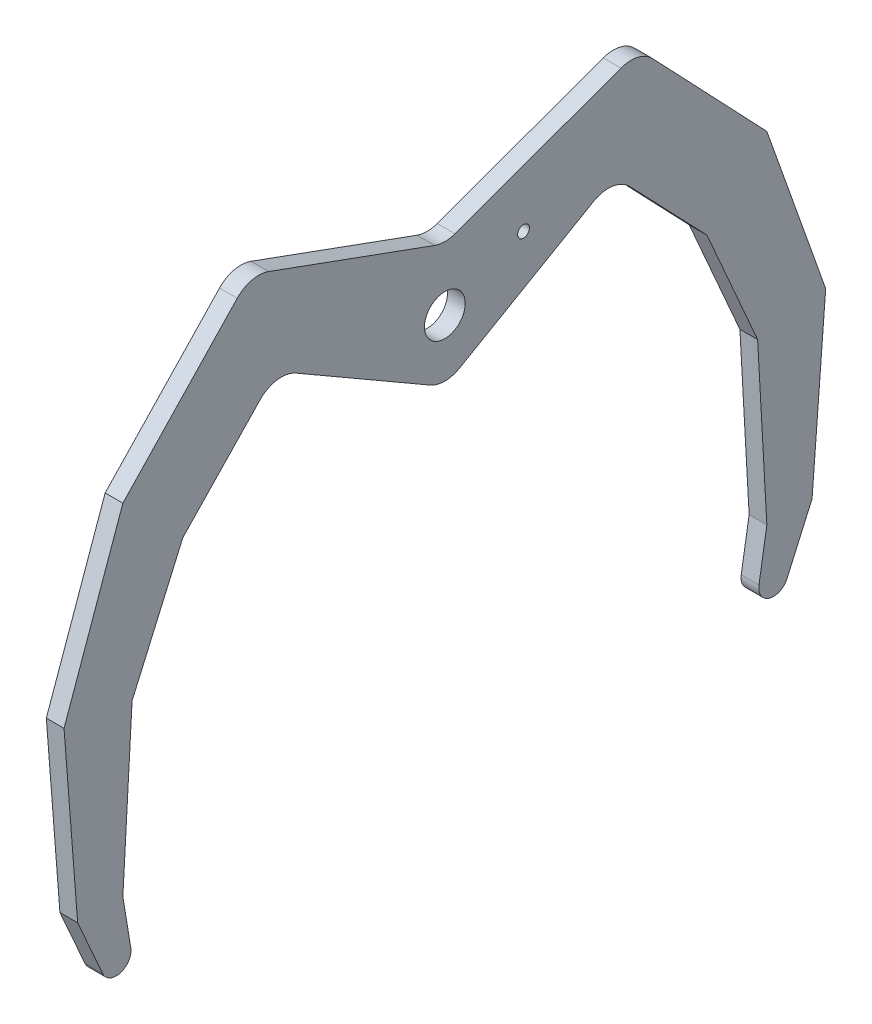
SolidWorks part; units mm, degrees
ref_plane "Front Plane" through (0, 0, 0) normal (0, 0, 1) x (1, 0, 0)
ref_plane "Top Plane" through (0, 0, 0) normal (0, 1, 0) x (1, 0, 0)
ref_plane "Right Plane" through (0, 0, 0) normal (1, 0, 0) x (0, 0, -1)
sketch "Sketch1" plane through (0, 0, 0) normal (1, 0, 0) x (0, 0, -1)
  line L0 (0, 15.8908) -> (0, -85.45) construction
  line L1 (1.7101, 11.0724) -> (29.8122, 21.3008)
  line L2 (2.5, -9.0066) -> (25.1791, 4.0871)
  line L3 (0, -85.45) -> (50, -85.45) construction
  line L4 (44.3608, -10.45) -> (31.2923, 3.213)
  line L5 (44.3608, -10.45) -> (52.94, -30.0455)
  line L6 (52.94, -30.0455) -> (54.5035, -58.0021)
  line L7 (54.5035, -58.0021) -> (53.1654, -66.1575)
  line L8 (-62.1586, -58.0021) -> (-64.4625, -28.3423)
  line L9 (-52.94, -30.0455) -> (-54.5035, -58.0021)
  line L10 (-64.4625, -28.3423) -> (-54.5035, -0.3096)
  line L11 (-44.3608, -10.45) -> (-52.94, -30.0455)
  line L12 (-44.3608, -10.45) -> (-31.2923, 3.213)
  line L13 (-54.5035, -0.3096) -> (-35.1457, 20.0478)
  line L14 (-2.5, -9.0066) -> (-25.1791, 4.0871)
  line L15 (-1.7101, 11.0724) -> (-29.8122, 21.3008)
  line L16 (62.1586, -58.0021) -> (57.9182, -67.5748)
  line L17 (62.1586, -58.0021) -> (64.4625, -28.3423)
  line L18 (64.4625, -28.3423) -> (54.5035, -0.3096)
  line L19 (54.5035, -0.3096) -> (35.1457, 20.0478)
  line L20 (-50.0689, 18.9616) -> (-69.3664, -3.6794) [skipped]
  line L21 (-69.3664, -3.6794) -> (-77.7866, -32.2121) [skipped]
  line L22 (-77.7866, -32.2121) -> (-73.8735, -61.7028) [skipped]
  line L23 (-73.8735, -61.7028) -> (-58.3038, -87.0523) [skipped]
  line L24 (-58.3038, -87.0523) -> (-33.7696, -103.8774) [skipped]
  line L25 (6.5074, 32.6053) -> (-8.3617, 32.2008) [skipped]
  line L26 (-23.2308, 31.7963) -> (-36.6498, 25.379) [skipped]
  line L27 (34.0036, 21.2488) -> (20.2555, 26.9271) [skipped]
  line L28 (24.407, -102.2948) -> (36.1986, -93.2277) [skipped]
  line L29 (-4.5131, -109.269) -> (9.947, -105.7819) [skipped]
  line L30 (-33.7696, -103.8774) -> (-4.5131, -109.269) [skipped]
  line L31 (-54.5035, -58.0021) -> (-53.1654, -66.1575)
  line L32 (-62.1586, -58.0021) -> (-57.9182, -67.5748)
  line L33 (57.1307, -67.2849) -> (62.1586, -58.0021) [skipped]
  line L34 (0, 0) -> (13.3104, 5.6247) construction
  circle A0 centre (0, 0) radius 3.45
  arc A1 (53.1654, -66.1575) -> (57.9182, -67.5748) centre (55.6324, -66.5622) ccw
  arc A2 (-29.8122, 21.3008) -> (-35.1457, 20.0478) centre (-31.5223, 16.6023) ccw
  arc A3 (-53.1654, -66.1575) -> (-57.9182, -67.5748) centre (-55.6324, -66.5622) cw
  arc A4 (29.8122, 21.3008) -> (35.1457, 20.0478) centre (31.5223, 16.6023) cw
  arc A5 (31.2923, 3.213) -> (25.1791, 4.0871) centre (27.6791, -0.243) ccw
  arc A6 (-31.2923, 3.213) -> (-25.1791, 4.0871) centre (-27.6791, -0.243) cw
  arc A7 (1.7101, 11.0724) -> (-1.7101, 11.0724) centre (0, 15.7709) cw
  arc A8 (2.5, -9.0066) -> (-2.5, -9.0066) centre (0, -4.6765) cw
  circle A9 centre (13.3104, 5.6247) radius 1
  point P56 (28.5788, 6.05)
  point P59 (32.8892, 22.4207)
  point P64 (28.5788, 6.05)
  point P68 (0, 10.45)
  point P71 (0, -10.45)
  point P73 (-28.5788, 6.05)
  dimension "D1" = 3.45
  dimension "D6" = 2.5
  dimension "D7" = 5
  dimension "D2" = 70
  dimension "D3" = 60
  dimension "D4" = 35
  dimension "D5" = 33
  dimension "D8" = 50
  dimension "D9" = 75
extrude "Boss-Extrude1" add sketch "Sketch1" along normal blind 3
